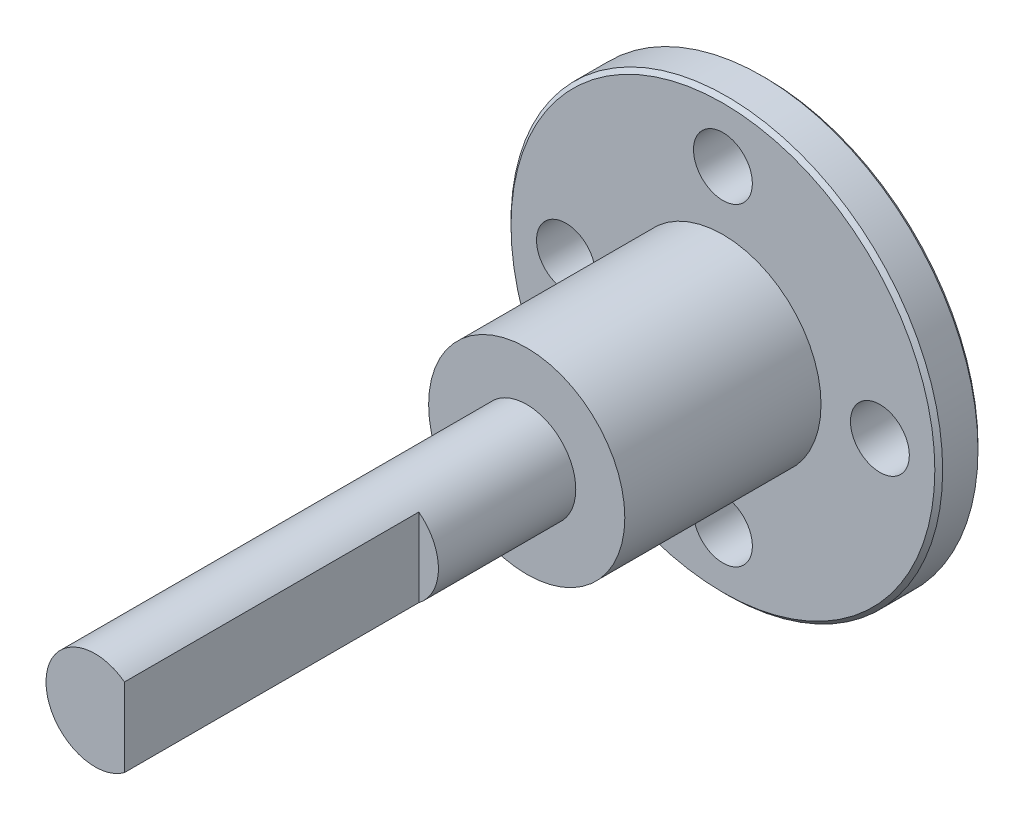
SolidWorks part; units mm, degrees
material "AISI 304"
ref_plane "前视基准面" through (0, 0, 0) normal (0, 0, 1) x (1, 0, 0)
ref_plane "上视基准面" through (0, 0, 0) normal (0, 1, 0) x (1, 0, 0)
ref_plane "右视基准面" through (0, 0, 0) normal (1, 0, 0) x (0, 0, -1)
sketch "草图1" plane through (0, 0, 0) normal (0, 0, 1) x (1, 0, 0)
  circle A3 centre (0, 0) radius 5
  circle A4 centre (0, 0) radius 11
  point P7 (0, 0)
  dimension "D1" = 22
  dimension "D2" = 10
extrude "凸台-拉伸1" add sketch "草图1" along normal blind 2.2 contours A3 | A4 A3 region at (0, 0, 0) region at (-10.6889, 0, 0)
sketch "草图2" plane through (0, 0, 2.2) normal (0, 0, 1) x (1, 0, 0)
  circle A0 centre (0, 0) radius 5
  dimension "D1" = 10
extrude "凸台-拉伸2" add sketch "草图2" along normal blind 10
hole_wizard "Ø3.0mm 暗销孔1" positions "草图8" profile "草图9" hole size "Ø3.0" standard "GB" end condition through all
sketch "草图8" plane through (0, 0, 2.2) normal (0, 0, 1) x (1, 0, 0)
  line L0 (0, 0) -> (0, 8) construction
  point P0 (0, 8)
  dimension "D1" = 8
sketch "草图9" plane through (0, 8, 2.2) normal (1, 0, 0) x (0, -1, 0)
  line L0 (0, 0) -> (0, 2.2)
  line L1 (0, 2.2) -> (1.5, 2.2)
  line L2 (1.5, 2.2) -> (1.5, 0)
  line L5 (1.5, 0) -> (0, 0)
  line L11 (0, -6.35) -> (0, 107.95) construction
  dimension "通孔孔直径" = 3
  dimension "通孔孔深度" = 2.2
pattern_circular "阵列(圆周)1" count 4 over 360 about axis through (0, 0, 2.2) along (0, 0, -1) of "Ø3.0mm 暗销孔1"
chamfer "倒角3" distance 0.2 angle 45 2 edges at (11, 0, 0) (11, 0, 2.2)
sketch "草图12" plane through (0, 0, 2.2) normal (0, 0, 1) x (1, 0, 0)
  circle A0 centre (0, 0) radius 2.5
  dimension "D1" = 5
extrude "轴" add sketch "草图12" along normal blind 32
sketch "草图13" plane through (0, 0, 34.2) normal (0, 0, 1) x (1, 0, 0)
  line L0 (0, 0) -> (4.1196, 0) construction
  line L1 (1.5, 2.6158) -> (1.5, -2.6158)
  circle A0 centre (0, 0) radius 2.5 construction
  circle A1 centre (0, 0) radius 2.5
  point P6 (1.5, 0)
  circle M2 centre (0, 0) radius 2.5
  dimension "D1" = 1.5
extrude "切除-拉伸1" cut sketch "草图13" against normal blind 15 contours L0 L1 M2 | L1 L0 A1 region at (1.9078, 0.775, 34.2) region at (1.9078, -0.775, 34.2)
